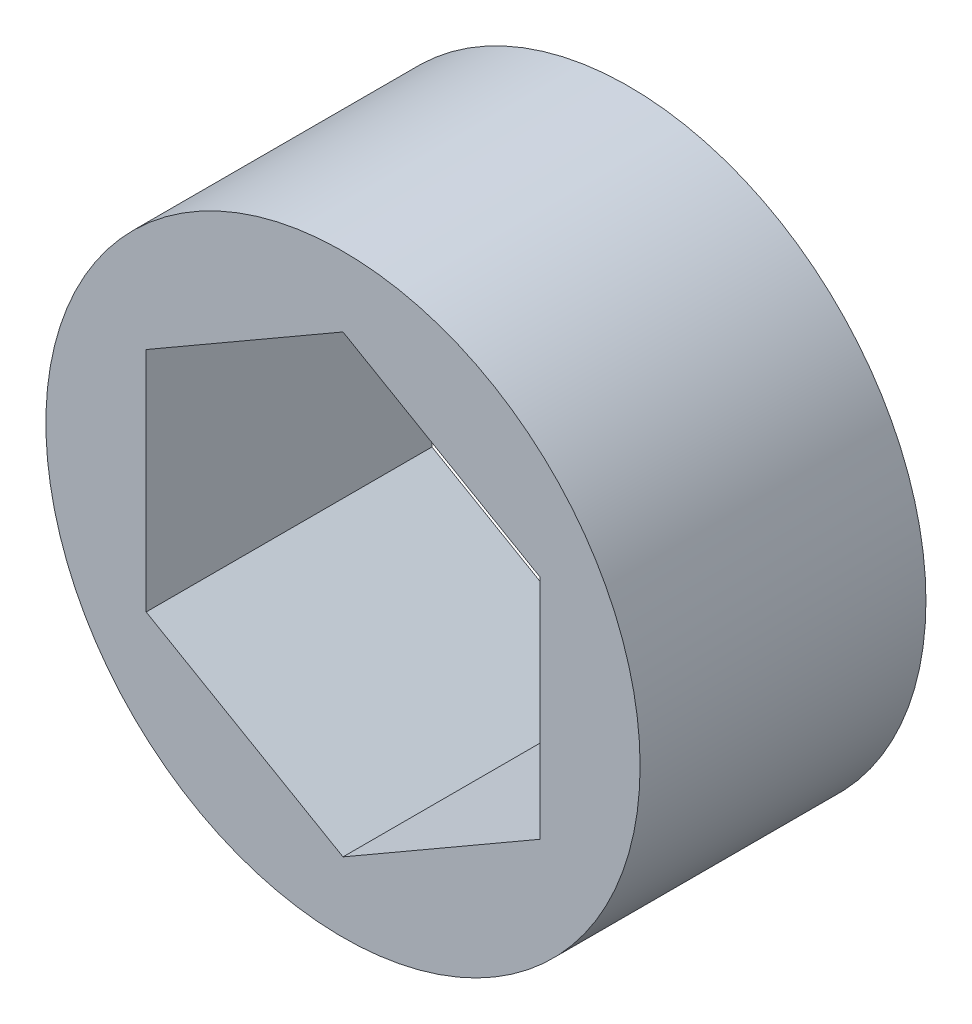
SolidWorks part; units mm, degrees
material "PET"
ref_plane "Front Plane" through (0, 0, 0) normal (0, 0, 1) x (1, 0, 0)
ref_plane "Top Plane" through (0, 0, 0) normal (0, 1, 0) x (1, 0, 0)
ref_plane "Right Plane" through (0, 0, 0) normal (1, 0, 0) x (0, 0, -1)
sketch "Sketch1" plane through (0, 0, 0) normal (0, 0, 1) x (1, 0, 0)
  line L1 (6.731, 3.8861) -> (0, 7.7723)
  line L2 (0, 7.7723) -> (-6.731, 3.8861)
  line L3 (-6.731, 3.8861) -> (-6.731, -3.8861)
  line L4 (-6.731, -3.8861) -> (0, -7.7723)
  line L5 (0, -7.7723) -> (6.731, -3.8861)
  line L6 (6.731, -3.8861) -> (6.731, 3.8861)
  circle A0 centre (0, 0) radius 6.731 construction
  circle A1 centre (0, 0) radius 10.16
  dimension "D1" = 13.462
  dimension "D2" = 20.32
extrude "Boss-Extrude1" add sketch "Sketch1" along normal blind 9.7739
